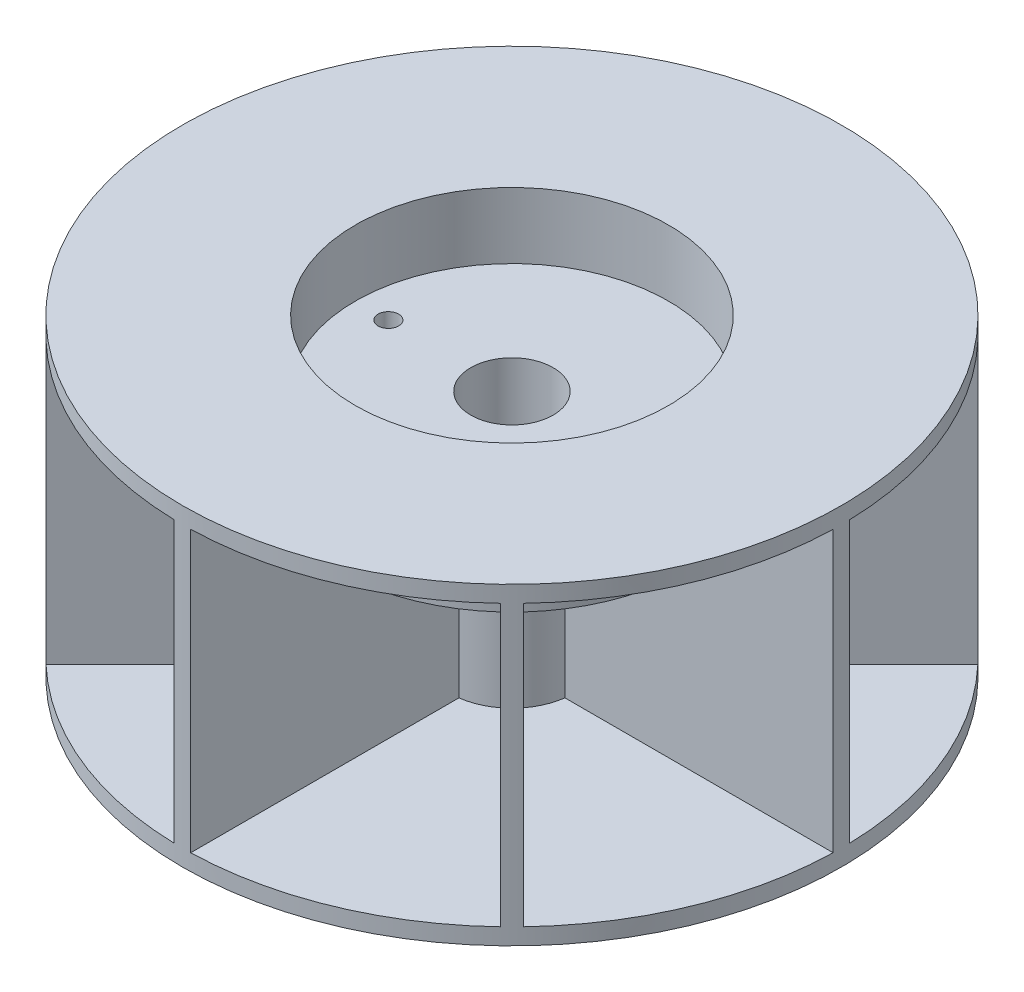
SolidWorks part; units mm, degrees
ref_plane "Front Plane" through (0, 0, 0) normal (0, 0, 1) x (1, 0, 0)
ref_plane "Top Plane" through (0, 0, 0) normal (0, 1, 0) x (1, 0, 0)
ref_plane "Right Plane" through (0, 0, 0) normal (1, 0, 0) x (0, 0, -1)
sketch "Sketch1" plane through (0, 0, 0) normal (0, 1, 0) x (1, 0, 0)
  circle A0 centre (0, 0) radius 3.175
  circle A1 centre (0, 0) radius 25.4
  dimension "D1" = 6.35
  dimension "D2" = 50.8
extrude "Boss-Extrude1" add sketch "Sketch1" along normal blind 1.27
sketch "Sketch2" plane through (0, 1.27, 0) normal (0, 1, 0) x (1, 0, 0)
  line L0 (0, 25.4) -> (0, 3.175)
  line L1 (-0.635, 25.3921) -> (-0.635, 3.1109)
  line L2 (0.635, 25.3921) -> (0.635, 3.1109)
  line L3 (18.4039, 17.5059) -> (2.6487, 1.7507)
  line L4 (17.5059, 18.4039) -> (1.7507, 2.6487)
  line L5 (25.3921, -0.635) -> (3.1109, -0.635)
  line L6 (25.3921, 0.635) -> (3.1109, 0.635)
  line L7 (17.5059, -18.4039) -> (1.7507, -2.6487)
  line L8 (18.4039, -17.5059) -> (2.6487, -1.7507)
  line L9 (-0.635, -25.3921) -> (-0.635, -3.1109)
  line L10 (0.635, -25.3921) -> (0.635, -3.1109)
  line L11 (-18.4039, -17.5059) -> (-2.6487, -1.7507)
  line L12 (-17.5059, -18.4039) -> (-1.7507, -2.6487)
  line L13 (-25.3921, 0.635) -> (-3.1109, 0.635)
  line L14 (-25.3921, -0.635) -> (-3.1109, -0.635)
  line L15 (-17.5059, 18.4039) -> (-1.7507, 2.6487)
  line L16 (-18.4039, 17.5059) -> (-2.6487, 1.7507)
  circle A0 centre (0, 0) radius 25.4 construction
  circle A1 centre (0, 0) radius 3.175 construction
  circle A2 centre (0, 0) radius 25.4
  circle A3 centre (0, 0) radius 3.175
  circle A4 centre (0, 0) radius 25.4 construction
  circle A5 centre (0, 0) radius 4.7625
  point P42 (0, 0)
  circle M4 centre (0, 0) radius 25.4
  circle M5 centre (0, 0) radius 3.175
  dimension "D1" = 0.635
  dimension "D4" = 9.525
  dimension "D3" = 8
  dimension "D2" = 0.635
extrude "Boss-Extrude4" add sketch "Sketch2" along normal blind 12.7 contours L1 L0 M4 M5 | L2 L0 M4 M5 | L4 L3 M4 M5 | L6 L5 M4 M5 | L8 L7 M4 M5 | L10 L9 M4 M5 | L12 L11 M4 M5 | L14 L13 M4 M5 | L16 L15 M4 M5 | L6 A5 L3 M5 | L5 A5 L6 M5 | L8 A5 L5 M5 | L7 A5 L8 M5 | L10 A5 L7 M5 | L9 A5 L10 M5 | L12 A5 L9 M5 | L11 A5 L12 M5 | L14 A5 L11 M5 | L13 A5 L14 M5 | L16 A5 L13 M5 | L15 A5 L16 M5 | L1 A5 L15 M5 | L0 A5 L1 M5 | L2 A5 L0 M5 | L4 A5 L2 M5 | L3 A5 L4 M5 region at (0.3176, 1.27, -15.0728) region at (-0.3176, 1.27, -15.0728) region at (0.3182, 1.27, -3.951) region at (-0.3182, 1.27, -3.951) region at (1.5388, 1.27, -3.7149) region at (-1.5388, 1.27, -3.7149) region at (10.6581, 1.27, -10.6581) region at (-10.6581, 1.27, -10.6581) region at (2.7938, 1.27, -2.7938) region at (-2.7938, 1.27, -2.7938) region at (3.7149, 1.27, -1.5388) region at (-3.7149, 1.27, -1.5388) region at (15.0728, 1.27, 0) region at (-15.0728, 1.27, 0) region at (3.951, 1.27, 0) region at (-3.951, 1.27, 0) region at (-3.7149, 1.27, 1.5388) region at (-10.6581, 1.27, 10.6581) region at (3.7149, 1.27, 1.5388) region at (-2.7938, 1.27, 2.7938) region at (10.6581, 1.27, 10.6581) region at (2.7938, 1.27, 2.7938) region at (-1.5388, 1.27, 3.7149) region at (0, 1.27, 15.0728) region at (1.5388, 1.27, 3.7149) region at (0, 1.27, 3.951)
sketch "Sketch5" plane through (0, 13.97, 0) normal (0, 1, 0) x (1, 0, 0)
  line L0 (0.635, -12.0483) -> (0.635, -25.3921)
  line L1 (0.635, -25.3921) -> (0.635, -4.72) construction
  line L2 (-0.635, -25.3921) -> (-0.635, -12.0483)
  line L3 (-0.635, -25.3921) -> (-0.635, -4.72) construction
  line L4 (-8.0704, -8.9684) -> (-17.5059, -18.4039)
  line L5 (-18.4039, -17.5059) -> (-8.9684, -8.0704)
  line L6 (-12.0483, -0.635) -> (-25.3921, -0.635)
  line L7 (-25.3921, 0.635) -> (-12.0483, 0.635)
  line L8 (-8.9684, 8.0704) -> (-18.4039, 17.5059)
  line L9 (-17.5059, 18.4039) -> (-8.0704, 8.9684)
  line L10 (-0.635, 12.0483) -> (-0.635, 25.3921)
  line L11 (0.635, 25.3921) -> (0.635, 12.0483)
  line L12 (8.0704, 8.9684) -> (17.5059, 18.4039)
  line L13 (18.4039, 17.5059) -> (8.9684, 8.0704)
  line L14 (12.0483, 0.635) -> (25.3921, 0.635)
  line L15 (25.3921, -0.635) -> (12.0483, -0.635)
  line L16 (8.9684, -8.0704) -> (18.4039, -17.5059)
  line L17 (17.5059, -18.4039) -> (8.0704, -8.9684)
  circle A0 centre (0, 0) radius 3.175
  circle A1 centre (0, 0) radius 12.065
  circle A2 centre (0, 0) radius 25.4
  circle A3 centre (0, 0) radius 13.6525
  point P45 (0, 0)
  circle M3 centre (0, 0) radius 3.175
  line M4 (17.5059, 18.4039) -> (2.8885, 3.7865)
  arc M5 (2.8885, 3.7865) -> (0.635, 4.72) centre (0, 0) ccw
  line M6 (0.635, 4.72) -> (0.635, 25.3921)
  arc M7 (0.635, 25.3921) -> (-0.635, 25.3921) centre (0, 0) ccw
  line M8 (-0.635, 25.3921) -> (-0.635, 4.72)
  arc M9 (-0.635, 4.72) -> (-2.8885, 3.7865) centre (0, 0) ccw
  line M10 (-2.8885, 3.7865) -> (-17.5059, 18.4039)
  arc M11 (-17.5059, 18.4039) -> (-18.4039, 17.5059) centre (0, 0) ccw
  line M12 (-18.4039, 17.5059) -> (-3.7865, 2.8885)
  arc M13 (-3.7865, 2.8885) -> (-4.72, 0.635) centre (0, 0) ccw
  line M14 (-4.72, 0.635) -> (-25.3921, 0.635)
  arc M15 (-25.3921, 0.635) -> (-25.3921, -0.635) centre (0, 0) ccw
  line M16 (-25.3921, -0.635) -> (-4.72, -0.635)
  arc M17 (-4.72, -0.635) -> (-3.7865, -2.8885) centre (0, 0) ccw
  line M18 (-3.7865, -2.8885) -> (-18.4039, -17.5059)
  arc M19 (-18.4039, -17.5059) -> (-17.5059, -18.4039) centre (0, 0) ccw
  line M20 (-17.5059, -18.4039) -> (-2.8885, -3.7865)
  arc M21 (-2.8885, -3.7865) -> (-0.635, -4.72) centre (0, 0) ccw
  line M22 (-0.635, -4.72) -> (-0.635, -25.3921)
  arc M23 (-0.635, -25.3921) -> (0.635, -25.3921) centre (0, 0) ccw
  line M24 (0.635, -25.3921) -> (0.635, -4.72)
  arc M25 (0.635, -4.72) -> (2.8885, -3.7865) centre (0, 0) ccw
  line M26 (2.8885, -3.7865) -> (17.5059, -18.4039)
  arc M27 (17.5059, -18.4039) -> (18.4039, -17.5059) centre (0, 0) ccw
  line M28 (18.4039, -17.5059) -> (3.7865, -2.8885)
  arc M29 (3.7865, -2.8885) -> (4.72, -0.635) centre (0, 0) ccw
  line M30 (4.72, -0.635) -> (25.3921, -0.635)
  arc M31 (25.3921, -0.635) -> (25.3921, 0.635) centre (0, 0) ccw
  line M32 (25.3921, 0.635) -> (4.72, 0.635)
  arc M33 (4.72, 0.635) -> (3.7865, 2.8885) centre (0, 0) ccw
  line M34 (3.7865, 2.8885) -> (18.4039, 17.5059)
  arc M35 (18.4039, 17.5059) -> (17.5059, 18.4039) centre (0, 0) ccw
  dimension "D1" = 24.13
  dimension "D3" = 1.5875
  dimension "D2" = 8
extrude "Boss-Extrude6" add sketch "Sketch5" along normal blind 2.54 contours A1 M28 M30 M29 | A1 M26 M28 M29 M30 M32 M33 M34 M4 M5 M6 M8 M9 M10 M12 M13 M14 M16 M17 M18 M20 M21 M22 M24 M25 M3 | A1 M24 M26 M25 | A1 M20 M22 M21 | A1 M16 M18 M17 | A1 M12 M14 M13 | A1 M8 M10 M9 | A1 M4 M6 M5 | A1 M32 M34 M33 region at (3.4102, 13.97, 8.2328) region at (0, 13.97, 11.7238) region at (-3.4102, 13.97, 8.2328) region at (8.2328, 13.97, 3.4102) region at (-8.2328, 13.97, 3.4102) region at (-8.2328, 13.97, -3.4102) region at (8.2328, 13.97, -3.4102) region at (-3.4102, 13.97, -8.2328) region at (3.4102, 13.97, -8.2328)
sketch "Sketch9" plane through (0, 16.51, 0) normal (0, 1, 0) x (1, 0, 0)
  circle A0 centre (0, 0) radius 3.175
  circle A1 centre (0, 0) radius 12.065
  dimension "D1" = 24.13
extrude "Boss-Extrude11" add sketch "Sketch9" along normal blind 2.54
extrude "Boss-Extrude7" add sketch "Sketch5<4>" along normal blind 8.89 contours A1 M22 M23 M24 | A1 M26 M27 M28 | A1 M30 M31 M32 | A1 M34 M35 M4 | A1 M6 M7 M8 | A1 M10 M11 M12 | A1 M14 M15 M16 | A1 M18 M19 M20 | L16 A3 A1 M30 | A3 L16 A1 M26 | L0 A3 A1 M26 | A3 L0 A1 M22 | L4 A3 A1 M22 | A3 L4 A1 M18 | L6 A3 A1 M18 | A3 L6 A1 M14 | L8 A3 A1 M14 | A3 L8 A1 M10 | L10 A3 A1 M10 | A3 L10 A1 M6 | L12 A3 A1 M6 | A3 L12 A1 M34 | L14 A3 A1 M34 | A3 L14 A1 M30 region at (4.8317, 13.97, 11.6648) region at (0, 13.97, 12.8535) region at (0, 13.97, 19.5225) region at (-4.8317, 13.97, 11.6648) region at (9.0888, 13.97, 9.0888) region at (13.8045, 13.97, 13.8045) region at (-9.0888, 13.97, 9.0888) region at (11.6648, 13.97, 4.8317) region at (-13.8045, 13.97, 13.8045) region at (-11.6648, 13.97, 4.8317) region at (12.8535, 13.97, 0) region at (19.5225, 13.97, 0) region at (-12.8535, 13.97, 0) region at (-19.5225, 13.97, 0) region at (-11.6648, 13.97, -4.8317) region at (11.6648, 13.97, -4.8317) region at (-9.0888, 13.97, -9.0888) region at (9.0888, 13.97, -9.0888) region at (-13.8045, 13.97, -13.8045) region at (13.8045, 13.97, -13.8045) region at (-4.8317, 13.97, -11.6648) region at (4.8317, 13.97, -11.6648) region at (0, 13.97, -12.8535) region at (0, 13.97, -19.5225)
sketch "Sketch5<4>" plane through (0, 13.97, 0) normal (0, 1, 0) x (1, 0, 0) same geometry as "Sketch5"
sketch "Sketch6" plane through (0, 22.86, 0) normal (0, 1, 0) x (1, 0, 0)
  circle A0 centre (0, 0) radius 12.065
  circle A1 centre (0, 0) radius 25.4
  circle A2 centre (0, 0) radius 12.065 construction
extrude "Boss-Extrude8" add sketch "Sketch6" along normal blind 1.27
hole_wizard "1/16 (0.0625) Diameter Hole1" positions "Sketch11" profile "Sketch12" hole size "1/16" standard "ANSI Inch"
sketch "Sketch11" plane through (0, 19.05, 0) normal (0, 1, 0) x (1, 0, 0)
  point P0 (-9.525, 0)
  point P2 (9.525, 0)
  point P6 (0, 0)
  dimension "D1" = 9.525
  dimension "D2" = 9.525
sketch "Sketch12" plane through (-9.525, 19.05, 0) normal (1, 0, 0) x (0, 0, 1)
  line L0 (0, 0) -> (0, 5.5569)
  line L1 (0, 5.5569) -> (0.7937, 5.08)
  line L2 (0.7937, 5.08) -> (0.7937, 0)
  line L5 (0.7937, 0) -> (0, 0)
  line L10 (0, 5.5569) -> (-0.7938, 5.08) construction
  line L11 (0, -6.35) -> (0, 107.95) construction
  dimension "Hole Dia." = 1.5875
  dimension "Hole Depth" = 5.08
  dimension "Drill Angle" = 118
